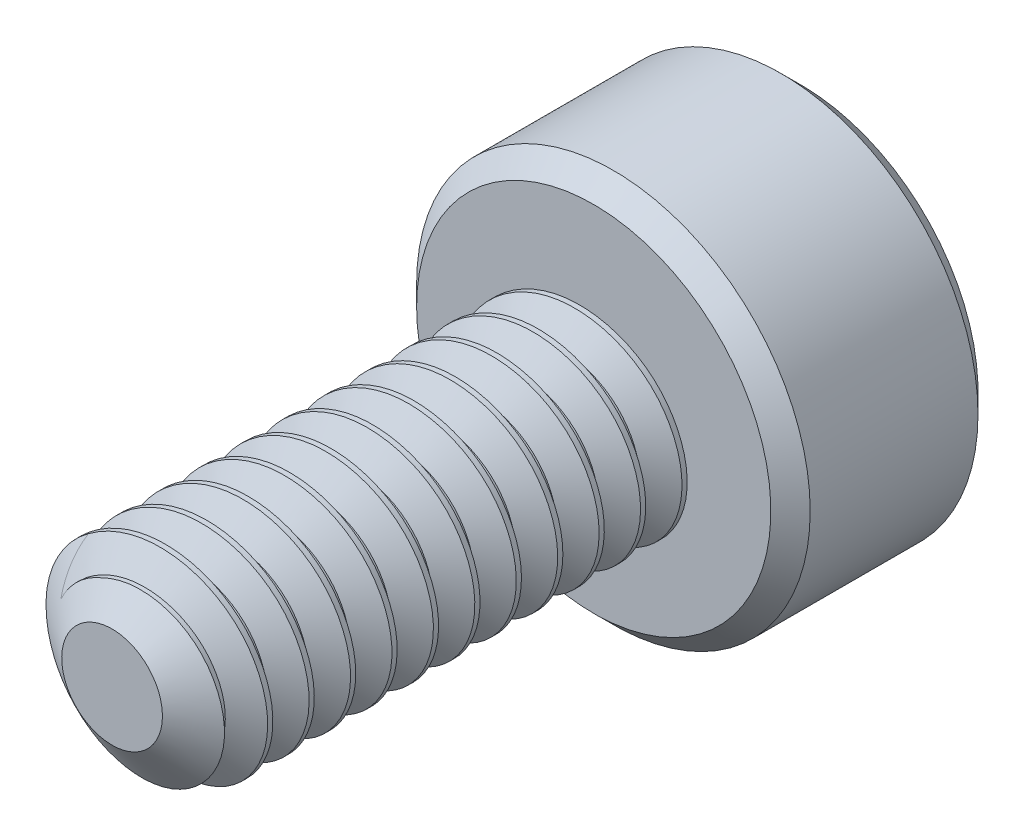
SolidWorks part; units mm, degrees
other "DetailItem1"
material "AISI Type 316L stainless steel"
ref_plane "Front Plane" through (0, 0, 0) normal (0, 0, 1) x (1, 0, 0)
ref_plane "Top Plane" through (0, 0, 0) normal (0, 1, 0) x (1, 0, 0)
ref_plane "Right Plane" through (0, 0, 0) normal (1, 0, 0) x (0, 0, -1)
sketch "Sketch1" plane through (0, 0, 0) normal (0, 0, 1) x (1, 0, 0)
  circle A0 centre (0, 0) radius 1
  dimension "OD" = 2
extrude "Extrude1" add sketch "Sketch1" against normal blind 4.65
sketch "Sketch2" plane through (0, 0, 0) normal (0, 0, 1) x (1, 0, 0)
  circle A0 centre (0, 0) radius 1 construction
  circle A1 centre (0, 0) radius 1
curve "Helix/Spiral1" pitch 0.4 height 5.05 radius 1 centre (0, 0, 0) axis (0, 0, -1) start towards (0, 1, 0) parameters "pitch"=0.4
sketch "Sketch3" plane through (0, 0, 0) normal (1, 0, 0) x (0, 0, -1)
  line L0 (-0.35, 1) -> (-0.2, 0.7402)
  line L1 (-0.2, 0.7402) -> (-0.15, 0.7402)
  line L2 (-0.15, 0.7402) -> (0, 1)
  line L3 (-0.35, 1) -> (0, 1)
  line L4 (-0.175, 1) -> (-0.175, 0.7402) construction
  line L5 (-0.275, 0.8701) -> (-0.075, 0.8701) construction
  line L6 (0, 1) -> (0, -1) construction
  dimension "D1" = 0.05
  dimension "D2" = 0.2
  dimension "D3" = 60
sweep "Cut-Sweep1" cut profiles "Sketch3" path "Helix/Spiral1" align with end faces yes
sketch "Sketch4" plane through (0, 0, 0) normal (1, 0, 0) x (0, 0, -1)
  line L0 (0.3598, 1) -> (0, 0.4862)
  line L1 (0, 0.4862) -> (0, 1)
  line L2 (0.3598, 1) -> (0, 1)
  line L3 (-0.35, 1) -> (0, 1) construction
  line L4 (0, 0) -> (7.0209, 0) construction
  dimension "D1" = 55
  dimension "D2" = 0.254
revolve "Cut-Revolve1" cut sketch "Sketch4" angle 360 about L4
sketch "Sketch6" plane through (0, 0, -4.65) normal (0, 0, -1) x (-1, 0, 0)
  circle A0 centre (0, 0) radius 1.9
  dimension "head dia" = 3.8
extrude "Extrude2" add sketch "Sketch6" along normal blind 2
sketch "Sketch7" plane through (0, 0, -6.65) normal (0, 0, -1) x (-1, 0, 0)
  line L1 (0, 0.866) -> (-0.75, 0.433)
  line L2 (-0.75, 0.433) -> (-0.75, -0.433)
  line L3 (-0.75, -0.433) -> (0, -0.866)
  line L4 (0, -0.866) -> (0.75, -0.433)
  line L5 (0.75, -0.433) -> (0.75, 0.433)
  line L6 (0.75, 0.433) -> (0, 0.866)
  circle A0 centre (0, 0) radius 0.75 construction
  dimension "hex dia" = 1.5
extrude "Cut-Extrude1" cut sketch "Sketch7" against normal blind 1.125
sketch "Sketch8" plane through (0, 0, -6.65) normal (0, 0, -1) x (-1, 0, 0)
  circle A0 centre (0, 0) radius 0.866
extrude "Cut-Extrude2" cut sketch "Sketch8" against normal through all draft 45
chamfer "Chamfer1" distance 0.19 angle 45 2 edges at (-1.9, 0, -6.65) (-1.9, 0, -4.65)
sketch "Sketch10" plane through (0, 0, -4.65) normal (0, 0, 1) x (1, 0, 0)
  circle A1 centre (0, 0) radius 1
  circle A2 centre (0, 0) radius 1
  dimension "D1" = 0
ref_plane "Plane1" through (0, 0, 0) normal (0, 0, 1) x (1, 0, 0)
extrude "partial thread" [suppressed] add sketch "Sketch10" along normal up to surface (36 mm away) separate body up to plane "Plane1"
chamfer "Chamfer2" [suppressed] distance 0.04 angle 45
combine bodies "Combine1" [suppressed] operation type add bodies to combine 107 108
sketch "Sketch9" plane through (0, 0, 0) normal (1, 0, 0) x (0, 0, -1)
  line L0 (0, 1) -> (0, -1) construction
  line L1 (1, 1) -> (1, -1) construction
  dimension "D1" = 1
equation "\"D3@Helix/Spiral1\" = \"screw length@Extrude1\"+\"pitch@Helix/Spiral1\""
equation "\"D1@Sketch3\" = \"pitch@Helix/Spiral1\"*.125"
equation "\"D2@Sketch3\" = \"pitch@Helix/Spiral1\"*.5"
equation "\"D1@Cut-Extrude1\" = \"hex dia@Sketch7\"*.75"
equation "\"D1@Chamfer1\" = \"head dia@Sketch6\"*.05"
equation "\"D1@Sketch9\" = \"pitch@Helix/Spiral1\"*2.5"
equation "\"D1@Chamfer2\"=\"OD@Sketch1\"*.02"
